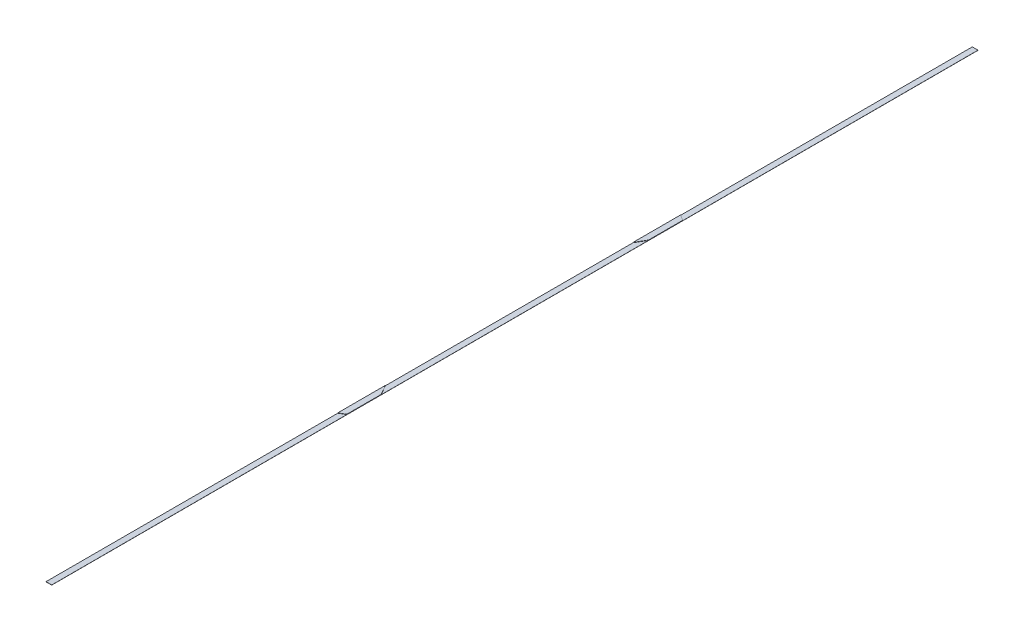
SolidWorks part; units mm, degrees
ref_plane "Front Plane" through (0, 0, 0) normal (0, 0, 1) x (1, 0, 0)
ref_plane "Top Plane" through (0, 0, 0) normal (0, 1, 0) x (1, 0, 0)
ref_plane "Right Plane" through (0, 0, 0) normal (1, 0, 0) x (0, 0, -1)
sketch "Sketch1" plane through (0, 0, 0) normal (0, 1, 0) x (1, 0, 0)
  line L1 (-25.4, 4111.9654) -> (25.4, 4111.9654)
  line L2 (-25.4, 4111.9654) -> (-25.4, -4111.9654)
  line L3 (-25.4, -4111.9654) -> (25.4, -4111.9654)
  line L4 (25.4, 4111.9654) -> (25.4, -4111.9654)
  line L5 (-25.4, 4111.9654) -> (25.4, -4111.9654) construction
  line L6 (-25.4, -4111.9654) -> (25.4, 4111.9654) construction
  point P0 (0, 0)
  dimension "D1" = 8223.9307
  dimension "D2" = 50.8
extrude "Boss-Extrude1" add sketch "Sketch1" along normal blind 1.27
sketch "Sketch3" plane through (0, 1.27, 0) normal (0, 1, 0) x (1, 0, 0)
  line L0 (-25.4, -1521.1654) -> (25.4, -1491.836)
  line L1 (-25.4, 4111.9654) -> (-25.4, -4111.9654) construction
  line L2 (25.4, -4111.9654) -> (25.4, 4111.9654) construction
  line L3 (25.4, -1491.836) -> (25.4, -1187.036)
  line L4 (25.4, -1187.036) -> (-25.4, -1099.0478)
  line L5 (-25.4, -4111.9654) -> (25.4, -4111.9654) construction
  line L6 (-25.4, 0) -> (25.4, 0) construction
  line L7 (25.4, 1187.036) -> (-25.4, 1099.0478)
  line L8 (-25.4, 1521.1654) -> (25.4, 1491.836)
  line L9 (-25.4, 1521.1654) -> (-25.4, 1099.0478)
  line L10 (25.4, -1491.836) -> (25.4, 0)
  line L11 (-25.4, 0) -> (-25.4, -1521.1654)
  line L12 (25.4, 1187.036) -> (25.4, 1491.836)
  line M4 (25.4, -4111.9654) -> (25.4, 4111.9654)
  line M6 (-25.4, 4111.9654) -> (-25.4, -4111.9654)
  dimension "D1" = 60
  dimension "D2" = 30
  dimension "D3" = 304.8
  dimension "D4" = 2590.8
extrude "Boss-Extrude2" add sketch "Sketch3" along normal blind 2.6568 contours L4 L0 M4 M6 | L9 L7 L12 L8 region at (-1.3664, 1.27, 1323.9824)
